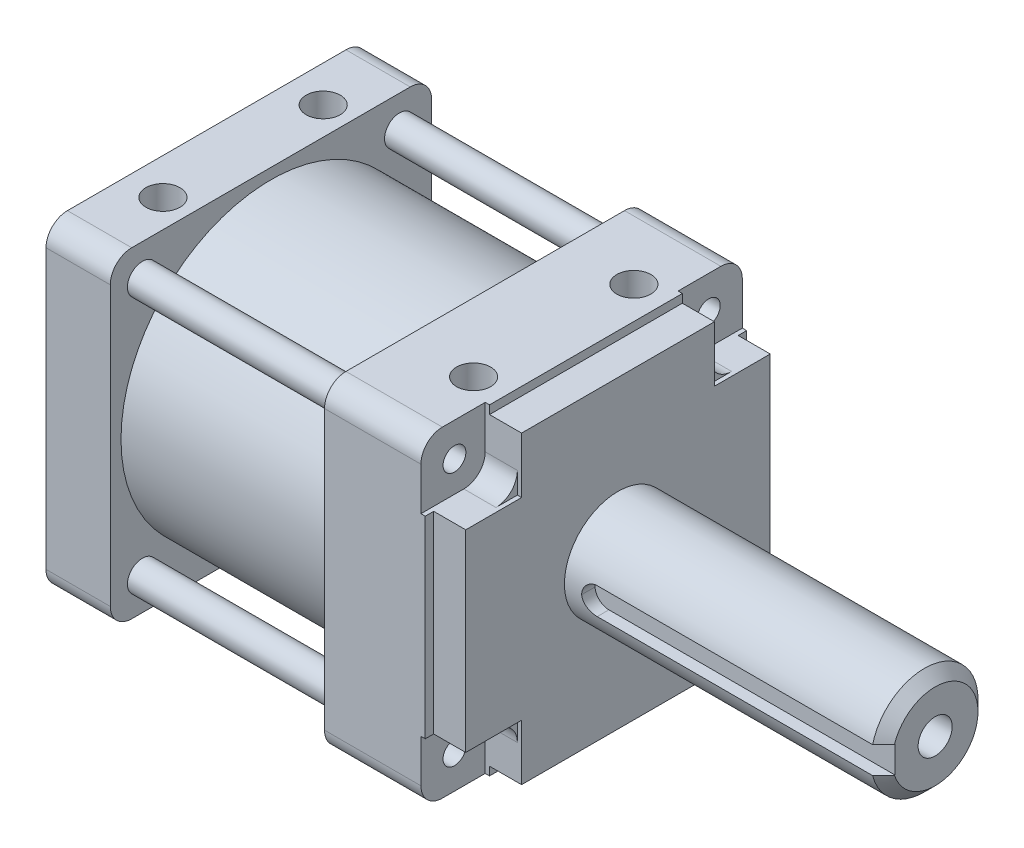
SolidWorks part; units mm, degrees
ref_plane "Plano frontal" through (0, 0, 0) normal (0, 0, 1) x (1, 0, 0)
ref_plane "Plano superior" through (0, 0, 0) normal (0, 1, 0) x (1, 0, 0)
ref_plane "Plano direito" through (0, 0, 0) normal (1, 0, 0) x (0, 0, -1)
sketch "Esboço2" plane through (0, 0, 0) normal (1, 0, 0) x (0, 0, -1)
  line L0 (2.54, 0) -> (35.56, 0)
  line L1 (38.1, 2.54) -> (38.1, 35.56)
  line L2 (35.56, 38.1) -> (2.54, 38.1)
  line L3 (0, 35.56) -> (0, 2.54)
  arc A0 (2.54, 38.1) -> (0, 35.56) centre (2.54, 35.56) ccw
  arc A1 (38.1, 35.56) -> (35.56, 38.1) centre (35.56, 35.56) ccw
  arc A2 (35.56, 0) -> (38.1, 2.54) centre (35.56, 2.54) ccw
  arc A3 (0, 2.54) -> (2.54, 0) centre (2.54, 2.54) ccw
  point P6 (0, 38.1)
  point P10 (38.1, 38.1)
  point P15 (0, 0)
  dimension "D3" = 2.54
  dimension "D1" = 38.1
  dimension "D2" = 38.1
extrude "Extrusão1" add sketch "Esboço2" against normal blind 15.24
sketch "Esboço3" plane through (0, 0, 0) normal (1, 0, 0) x (0, 0, -1)
  line L0 (0, 0) -> (7.62, 0)
  line L2 (7.62, 0) -> (7.62, 5.08)
  line L3 (5.08, 7.62) -> (0, 7.62)
  line L5 (0, 7.62) -> (0, 0)
  line L7 (30.48, 0) -> (38.1, 0)
  line L8 (38.1, 0) -> (38.1, 7.62)
  line L10 (0, 38.1) -> (0, 30.48)
  line L13 (7.62, 38.1) -> (0, 38.1)
  line L14 (30.48, 5.08) -> (30.48, 0)
  line L15 (30.48, 0) -> (38.1, 0)
  line L16 (38.1, 0) -> (38.1, 7.62)
  line L17 (38.1, 7.62) -> (33.02, 7.62)
  line L18 (0, 38.1) -> (0, 30.48)
  line L19 (0, 30.48) -> (5.08, 30.48)
  line L20 (7.62, 33.02) -> (7.62, 38.1)
  line L21 (7.62, 38.1) -> (0, 38.1)
  line L22 (30.48, 38.1) -> (30.48, 33.02)
  line L23 (33.02, 30.48) -> (38.1, 30.48)
  line L24 (38.1, 30.48) -> (38.1, 38.1)
  line L25 (38.1, 38.1) -> (30.48, 38.1)
  line L26 (0, 30.48) -> (5.08, 30.48) [skipped]
  line L27 (7.62, 33.02) -> (7.62, 38.1) [skipped]
  line L28 (38.1, 7.62) -> (33.02, 7.62) [skipped]
  line L29 (30.48, 5.08) -> (30.48, 0) [skipped]
  arc A0 (7.62, 33.02) -> (5.08, 30.48) centre (5.08, 33.02) cw
  arc A1 (33.02, 30.48) -> (30.48, 33.02) centre (33.02, 33.02) cw
  arc A2 (30.48, 5.08) -> (33.02, 7.62) centre (33.02, 5.08) cw
  arc A3 (7.62, 5.08) -> (5.08, 7.62) centre (5.08, 5.08) ccw
  arc M1 (2.54, 38.1) -> (0, 35.56) centre (2.54, 35.56) ccw
  line M2 (0, 35.56) -> (0, 2.54)
  arc M3 (0, 2.54) -> (2.54, 0) centre (2.54, 2.54) ccw
  line M4 (2.54, 0) -> (35.56, 0)
  arc M5 (35.56, 0) -> (38.1, 2.54) centre (35.56, 2.54) ccw
  line M6 (38.1, 2.54) -> (38.1, 35.56)
  arc M7 (38.1, 35.56) -> (35.56, 38.1) centre (35.56, 35.56) ccw
  line M8 (35.56, 38.1) -> (2.54, 38.1)
  dimension "D1" = 2.54
  dimension "D2" = 7.62
  dimension "D3" = 7.62
extrude "Extrusão2" cut sketch "Esboço3" against normal blind 3.81 contours A0 L20 L19 M8 M1 M2 | L2 A3 L3 M2 M3 M4 | A2 L14 L17 M4 M5 M6 | A1 L23 L22 M6 M7 M8
sketch "Esboço4" plane through (0, 0, 0) normal (1, 0, 0) x (0, 0, -1)
  line L0 (0, 30.48) -> (0, 7.62) construction
  line L1 (7.62, 0) -> (30.48, 0) construction
  circle A0 centre (19.05, 19.05) radius 6.35
  dimension "D1" = 19.05
  dimension "D2" = 19.05
extrude "Extrusão3" add sketch "Esboço4" along normal blind 38.1
sketch "Esboço5" plane through (-15.24, 0, 0) normal (-1, 0, 0) x (0, 0, 1)
  line L0 (0, 35.56) -> (0, 2.54) construction
  line L1 (-2.54, 0) -> (-35.56, 0) construction
  circle A0 centre (-19.05, 19.05) radius 17.78
  dimension "D1" = 19.05
  dimension "D2" = 19.05
extrude "Extrusão4" add sketch "Esboço5" along normal blind 25.4
sketch "Esboço6" plane through (-15.24, 0, 0) normal (-1, 0, 0) x (0, 0, 1)
  line L0 (0, 35.56) -> (0, 2.54) construction
  line L1 (-2.54, 0) -> (-35.56, 0) construction
  circle A0 centre (-3.81, 3.81) radius 1.778
  circle A1 centre (-34.29, 3.81) radius 1.778
  circle A2 centre (-3.81, 34.29) radius 1.778
  circle A3 centre (-34.29, 34.29) radius 1.778
  dimension "D1" = 3.81
  dimension "D2" = 3.81
extrude "Extrusão5" add sketch "Esboço6" along normal blind 25.4
sketch "Esboço7" plane through (-40.64, 0, 0) normal (-1, 0, 0) x (0, 0, 1)
  line L0 (-2.54, 0) -> (-35.56, 0)
  line L1 (-38.1, 2.54) -> (-38.1, 35.56)
  line L2 (-35.56, 38.1) -> (-2.54, 38.1)
  line L3 (0, 35.56) -> (0, 2.54)
  arc A0 (-2.54, 0) -> (0, 2.54) centre (-2.54, 2.54) ccw
  arc A1 (-2.54, 38.1) -> (0, 35.56) centre (-2.54, 35.56) cw
  arc A2 (-38.1, 35.56) -> (-35.56, 38.1) centre (-35.56, 35.56) cw
  arc A3 (-35.56, 0) -> (-38.1, 2.54) centre (-35.56, 2.54) cw
  point P7 (0, 0)
  dimension "D1" = 2.54
extrude "Extrusão6" add sketch "Esboço7" along normal blind 7.62
sketch "Esboço8" plane through (38.1, 0, 0) normal (1, 0, 0) x (0, 0, -1)
  line L1 (11.1125, 20.6375) -> (14.2875, 20.6375)
  line L2 (11.1125, 20.6375) -> (11.1125, 17.4625)
  line L3 (11.1125, 17.4625) -> (14.2875, 17.4625)
  line L4 (14.2875, 20.6375) -> (14.2875, 17.4625)
  line L5 (11.1125, 20.6375) -> (14.2875, 17.4625) construction
  line L6 (11.1125, 17.4625) -> (14.2875, 20.6375) construction
  circle A0 centre (19.05, 19.05) radius 6.35 construction
  circle A1 centre (19.05, 19.05) radius 6.35 construction
  point P0 (12.7, 19.05)
  point P11 (12.7, 19.05)
  dimension "D1" = 3.175
  dimension "D2" = 3.175
extrude "Extrusão8" cut sketch "Esboço8" against normal blind 35.56
fillet "Filete5" radius 1.651 1 edges at (2.54, 20.6375, -13.5946)
fillet "Filete6" radius 1.651 1 edges at (2.54, 17.4625, -13.5946)
chamfer "Chanfro1" distance 1.27 angle 45 1 edges at (38.1, 19.05, -25.4)
hole_wizard "#10-32 Tapped Hole3" positions "3DSketch4" profile "Esboço16" tap size "#10-32" standard "ANSI Inch"
sketch3d "3DSketch4"
  line L0 (0, 38.1, -30.48) -> (0, 38.1, -7.62) construction
  line L4 (-48.26, 38.1, -2.54) -> (-48.26, 38.1, -35.56) construction
  line L6 (0, 38.1, -19.05) -> (-48.26, 38.1, -19.05) construction
  point P0 (-7.12, 38.1, -9.55)
  point P2 (-7.12, 38.1, -28.55)
  point P4 (-43.95, 38.1, -9.55)
  point P6 (-43.95, 38.1, -28.55)
  point P28 (-6.7659, 0, 15.4655)
  point P32 (-7.6563, 0, 14.3753)
  dimension "D1" = 7.12
  dimension "D2" = 7.12
  dimension "D3" = 9.5
  dimension "D4" = 9.5
  dimension "D5" = 9.5
  dimension "D6" = 4.31
  dimension "D7" = 4.31
  dimension "D8" = 9.5
sketch "Esboço16" plane through (-7.12, 38.1, -9.55) normal (1, 0, 0) x (0, 0, 1)
  line L0 (0, 0) -> (0, 13.1513)
  line L1 (0, 13.1513) -> (2.0193, 11.938)
  line L2 (2.0193, 11.938) -> (2.0193, 0)
  line L5 (2.0193, 0) -> (0, 0)
  line L10 (0, 13.1513) -> (-2.0193, 11.938) construction
  line L11 (0, -6.35) -> (0, 107.95) construction
  dimension "Tap Drill Dia." = 4.0386
  dimension "Tap Drill Depth" = 11.938
  dimension "Drill Angle" = 118
cosmetic thread "Hole Thread2" parameters "D1"=9.652, "D2"=4.826
cosmetic thread "Hole Thread3" parameters "D1"=9.652, "D2"=4.826
cosmetic thread "Hole Thread4" parameters "D1"=9.652, "D2"=4.826
cosmetic thread "Hole Thread5" parameters "D1"=9.652, "D2"=4.826
cosmetic thread "Hole Thread6" parameters "D1"=9.652, "D2"=4.826
cosmetic thread "Hole Thread7" parameters "D1"=9.652, "D2"=4.826
sketch "Esboço17" plane through (-48.26, 0, 0) normal (-1, 0, 0) x (0, 0, 1)
  line L0 (-38.1, 19.05) -> (0, 19.05) construction
  line L1 (-38.1, 35.56) -> (-38.1, 2.54) construction
  line L2 (0, 2.54) -> (0, 35.56) construction
  line L3 (-19.05, 38.1) -> (-19.05, 0) construction
  line L4 (-2.54, 38.1) -> (-35.56, 38.1) construction
  line L5 (-35.56, 0) -> (-2.54, 0) construction
  circle A0 centre (-19.05, 19.05) radius 5
  dimension "D1" = 10
extrude "Corte-extrusão1" cut sketch "Esboço17" against normal blind 2.54
hole_wizard "#10-32 Tapped Hole1" positions "Sketch2" profile "Sketch3" tap size "#10-32" standard "ANSI Inch"
sketch "Sketch2" plane through (38.1, 0, 0) normal (1, 0, 0) x (0, 0, -1)
  point P0 (19.05, 19.05)
sketch "Sketch3" plane through (38.1, 19.05, -19.05) normal (0, 1, 0) x (0, 0, -1)
  line L0 (0, 0) -> (0, 11.2133)
  line L1 (0, 11.2133) -> (2.0193, 10)
  line L2 (2.0193, 10) -> (2.0193, 0)
  line L5 (2.0193, 0) -> (0, 0)
  line L10 (0, 11.2133) -> (-2.0193, 10) construction
  line L11 (0, -6.35) -> (0, 107.95) construction
  dimension "Tap Drill Dia." = 4.0386
  dimension "Tap Drill Depth" = 10
  dimension "Drill Angle" = 118
cosmetic thread "Hole Thread1" parameters "D1"=10, "D2"=4.826
sketch "Sketch4" plane through (0, 0, 0) normal (1, 0, 0) x (0, 0, -1)
  line L0 (30.48, 0) -> (7.62, 0)
  line L1 (7.62, 0) -> (7.62, 7.62)
  line L2 (7.62, 7.62) -> (0, 7.62)
  line L3 (0, 7.62) -> (0, 30.48)
  line L4 (0, 30.48) -> (7.62, 30.48)
  line L5 (7.62, 30.48) -> (7.62, 38.1)
  line L6 (7.62, 38.1) -> (30.48, 38.1)
  line L7 (30.48, 38.1) -> (7.62, 38.1) construction
  line L8 (30.48, 38.1) -> (30.48, 30.48)
  line L9 (30.48, 30.48) -> (38.1, 30.48)
  line L10 (38.1, 30.48) -> (38.1, 7.62)
  line L11 (38.1, 7.62) -> (30.48, 7.62)
  line L12 (30.48, 7.62) -> (30.48, 0)
extrude "Boss-Extrude1" add sketch "Sketch4" along normal blind 0.5
hole_wizard "#10-32 Tapped Hole2" positions "Sketch8" profile "Sketch6" tap size "#10-32" standard "ANSI Inch"
sketch "Sketch8" plane through (0, 0, 0) normal (0, -1, 0) x (1, 0, 0)
  line L0 (0.5, -19.05) -> (-48.26, -19.05) construction
  line L1 (0.5, -7.62) -> (0.5, -30.48) construction
  line L2 (-48.26, -35.56) -> (-48.26, -2.54) construction
  line L4 (-7.12, -28.55) -> (-54.6253, -28.55) construction
  line L6 (-7.12, -9.55) -> (-60.8076, -9.55) construction
  point P0 (-7.12, -9.55)
  point P2 (-7.12, -28.55)
  point P4 (-43.95, -9.55)
  point P6 (-43.95, -28.55)
  dimension "D1" = 9.5
  dimension "D2" = 9.5
  dimension "D3" = 7.62
  dimension "D4" = 7.62
  dimension "D5" = 4.31
  dimension "D6" = 4.31
sketch "Sketch6" plane through (-7.12, 0, -9.55) normal (1, 0, 0) x (0, 0, -1)
  line L0 (0, 0) -> (0, 13.1513)
  line L1 (0, 13.1513) -> (2.0193, 11.938)
  line L2 (2.0193, 11.938) -> (2.0193, 0)
  line L5 (2.0193, 0) -> (0, 0)
  line L10 (0, 13.1513) -> (-2.0193, 11.938) construction
  line L11 (0, -6.35) -> (0, 107.95) construction
  dimension "Tap Drill Dia." = 4.0386
  dimension "Tap Drill Depth" = 11.938
  dimension "Drill Angle" = 118
cosmetic thread "Hole Thread8" parameters "D1"=9.652, "D2"=4.826
cosmetic thread "Hole Thread9" parameters "D1"=9.652, "D2"=4.826
cosmetic thread "Hole Thread10" parameters "D1"=9.652, "D2"=4.826
cosmetic thread "Hole Thread11" parameters "D1"=9.652, "D2"=4.826
sketch "Sketch9" plane through (-3.81, 0, 0) normal (1, 0, 0) x (0, 0, -1)
  line L1 (3.975, 3.975) -> (34.125, 3.975)
  line L2 (3.975, 3.975) -> (3.975, 34.125)
  line L3 (3.975, 34.125) -> (34.125, 34.125)
  line L4 (34.125, 3.975) -> (34.125, 34.125)
  line L5 (3.975, 3.975) -> (34.125, 34.125) construction
  line L6 (3.975, 34.125) -> (34.125, 3.975) construction
  point P0 (19.05, 19.05)
hole_wizard "#6-32 Tapped Hole1" positions "Sketch13" profile "Sketch12" tap size "#6-32" standard "ANSI Inch"
sketch "Sketch13" plane through (-3.81, 0, 0) normal (1, 0, 0) x (0, 0, -1)
  point P0 (3.975, 34.125)
  point P3 (34.125, 34.125)
  point P6 (3.975, 3.975)
  point P9 (34.125, 3.975)
sketch "Sketch12" plane through (-3.81, 34.125, -3.975) normal (0, 1, 0) x (0, 0, -1)
  line L0 (0, 0) -> (0, 10.2107)
  line L1 (0, 10.2107) -> (1.3525, 9.398)
  line L2 (1.3525, 9.398) -> (1.3525, 0)
  line L5 (1.3525, 0) -> (0, 0)
  line L10 (0, 10.2107) -> (-1.3526, 9.398) construction
  line L11 (0, -6.35) -> (0, 107.95) construction
  dimension "Tap Drill Dia." = 2.7051
  dimension "Tap Drill Depth" = 9.398
  dimension "Drill Angle" = 118
cosmetic thread "Hole Thread12" parameters "D1"=7.112, "D2"=3.5052
cosmetic thread "Hole Thread13" parameters "D1"=7.112, "D2"=3.5052
cosmetic thread "Hole Thread14" parameters "D1"=7.112, "D2"=3.5052
cosmetic thread "Hole Thread15" parameters "D1"=7.112, "D2"=3.5052
sketch "Esboço18" plane through (0.5, 0, 0) normal (1, 0, 0) x (0, 0, -1)
  line L0 (5.08, 7.62) -> (0, 7.62) construction
  line L1 (0, 30.48) -> (1, 30.48)
  line L2 (0, 30.48) -> (0, 7.62)
  line L3 (0, 7.62) -> (1, 7.62)
  line L4 (1, 30.48) -> (1, 7.62)
  line L5 (30.48, 38.1) -> (30.48, 33.02) construction
  line L6 (7.62, 38.1) -> (30.48, 38.1)
  line L7 (7.62, 38.1) -> (7.62, 37.1)
  line L8 (7.62, 37.1) -> (30.48, 37.1)
  line L9 (30.48, 38.1) -> (30.48, 37.1)
  line L10 (30.48, 7.62) -> (38.1, 7.62) construction
  line L11 (38.1, 30.48) -> (37.1, 30.48)
  line L12 (38.1, 30.48) -> (38.1, 7.62)
  line L13 (38.1, 7.62) -> (37.1, 7.62)
  line L14 (37.1, 30.48) -> (37.1, 7.62)
  line L15 (30.48, 0) -> (30.48, 7.62) construction
  line L16 (7.62, 0) -> (30.48, 0)
  line L17 (7.62, 0) -> (7.62, 1)
  line L18 (7.62, 1) -> (30.48, 1)
  line L19 (30.48, 0) -> (30.48, 1)
  dimension "D1" = 1
  dimension "D2" = 1
  dimension "D3" = 1
  dimension "D4" = 1
extrude "Corte-extrusão2" cut sketch "Esboço18" against normal blind 3.8
